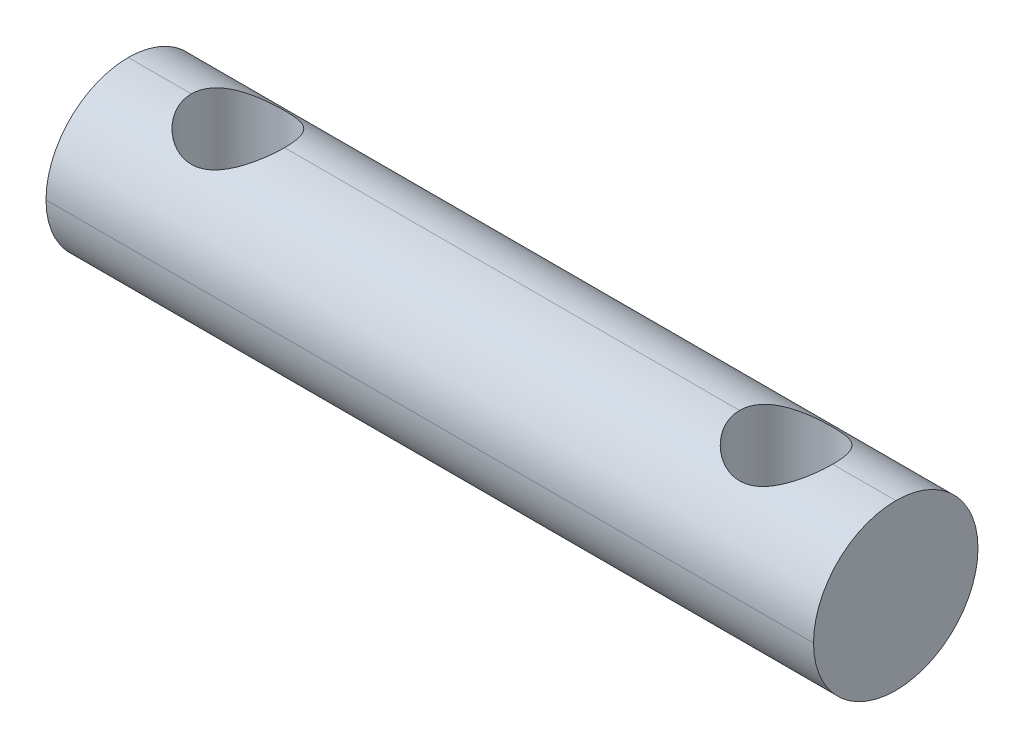
SolidWorks part; units mm, degrees
ref_plane "Front Plane" through (0, 0, 0) normal (0, 0, 1) x (1, 0, 0)
ref_plane "Top Plane" through (0, 0, 0) normal (0, 1, 0) x (1, 0, 0)
ref_plane "Right Plane" through (0, 0, 0) normal (1, 0, 0) x (0, 0, -1)
sketch "Sketch1" plane through (0, 0, 0) normal (0, 1, 0) x (1, 0, 0)
  line L1 (35, -7.5) -> (-35, -7.5)
  line L2 (35, -7.5) -> (35, 7.5)
  line L3 (35, 7.5) -> (-35, 7.5)
  line L4 (-35, -7.5) -> (-35, 7.5)
  line L5 (35, -7.5) -> (-35, 7.5) construction
  line L6 (35, 7.5) -> (-35, -7.5) construction
  circle A0 centre (-25, 0) radius 4.25
  circle A1 centre (25, 0) radius 4.25
  point P0 (0, 0)
  dimension "D5" = 8.5
  dimension "D1" = 15
  dimension "D2" = 70
  dimension "D3" = 25
  dimension "D4" = 25
extrude "Boss-Extrude1" add sketch "Sketch1" along normal blind 11
sketch "Sketch2" plane through (0, 0, 0) normal (0, -1, 0) x (1, 0, 0)
  line L1 (35, -7.5) -> (-35, -7.5)
  line L2 (35, -7.5) -> (35, 7.5)
  line L3 (35, 7.5) -> (-35, 7.5)
  line L4 (-35, -7.5) -> (-35, 7.5)
  line L5 (35, -7.5) -> (-35, 7.5) construction
  line L6 (35, 7.5) -> (-35, -7.5) construction
  point P0 (0, 0)
extrude "Boss-Extrude2" add sketch "Sketch2" along normal blind 4
fillet "Fillet1" radius 7.5 4 edges at (0, 11, 7.5) (0, 11, -7.5) (0, -4, 7.5) (0, -4, -7.5)
